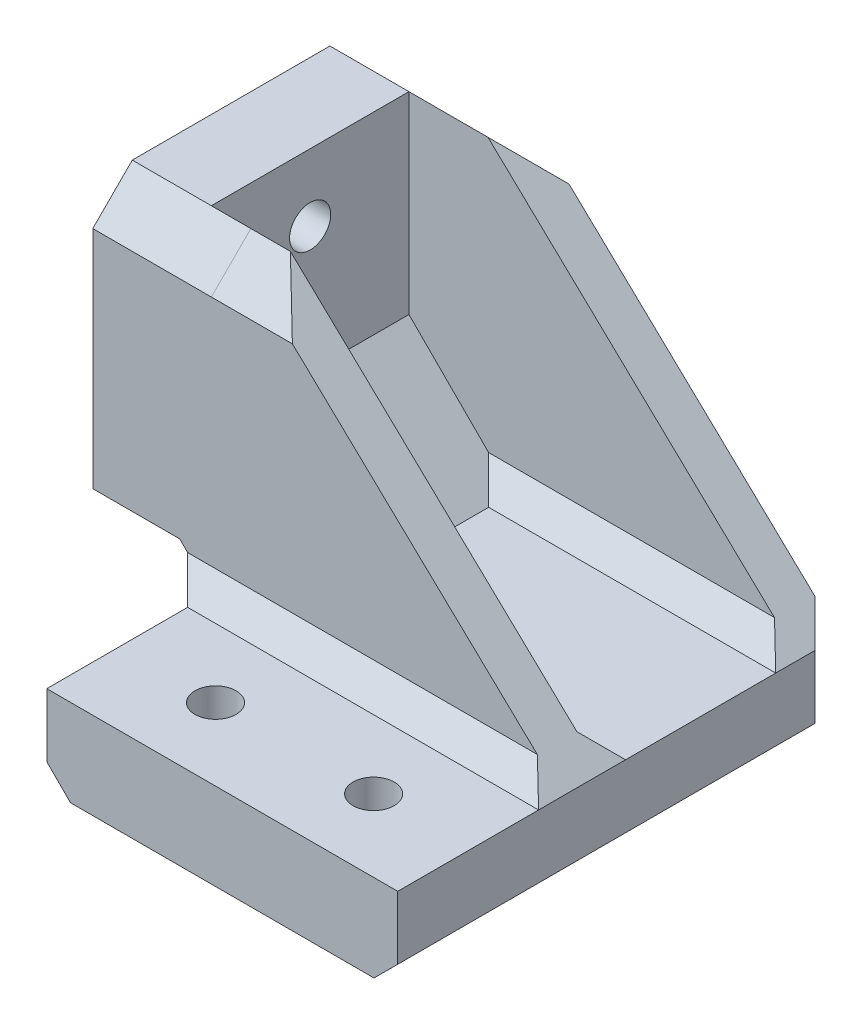
SolidWorks part; units mm, degrees
ref_plane "Front Plane" through (0, 0, 0) normal (0, 0, 1) x (1, 0, 0)
ref_plane "Top Plane" through (0, 0, 0) normal (0, 1, 0) x (1, 0, 0)
ref_plane "Right Plane" through (0, 0, 0) normal (1, 0, 0) x (0, 0, -1)
sketch "Sketch1" plane through (0, 0, 0) normal (0, 0, 1) x (1, 0, 0)
  line L0 (-22.2, 3) -> (-19.2, 0)
  line L1 (-19.2, 0) -> (19.2, 0)
  line L2 (19.2, 0) -> (22.2, 3)
  line L3 (22.2, 3) -> (22.2, 11)
  line L4 (22.2, 11) -> (-22.2, 11)
  line L5 (-22.2, 11) -> (-22.2, 3)
  line L6 (24.42, 0) -> (-24.42, 0) construction
  point P8 (0, 0)
sketch "Sketch2" plane through (0, 0, 0) normal (0, 1, 0) x (1, 0, 0)
  line L1 (-22.2, 0) -> (22.2, 0)
  line L2 (-22.2, 0) -> (-22.2, 55.82)
  line L3 (-22.2, 55.82) -> (22.2, 55.82)
  line L4 (22.2, 0) -> (22.2, 55.82)
  point P4 (0, 0)
  point P6 (0, 0)
  point P8 (0, 0)
  point P10 (-158.0606, 53.0935)
  dimension "D1" = 55.82
extrude "Boss-Extrude1" add sketch "Sketch2" along normal up to vertex (11 mm away) up to point (22.2, 11, 0)
chamfer "Chamfer1" distance 3 angle 45 2 edges at (22.2, 0, -27.91) (-22.2, 0, -27.91)
sketch "Sketch3" plane through (0, 11, 0) normal (0, 1, 0) x (1, 0, 0)
  line L0 (0, 0) -> (0, 9.15) construction
  line L1 (0, 9.15) -> (10, 9.15) construction
  line L2 (0, 9.15) -> (-10, 9.15) construction
  circle A0 centre (10, 9.15) radius 2.6
  circle A1 centre (-10, 9.15) radius 2.6
  dimension "D4" = 5.2
  dimension "D5" = 5.2
  dimension "D1" = 9.15
  dimension "D2" = 10
  dimension "D3" = 10
extrude "Cut-Extrude1" cut sketch "Sketch3" against normal through all
sketch "Sketch4" plane through (-22.2, 0, 0) normal (-1, 0, 0) x (0, 0, 1)
  line L0 (-38.32, 48.5) -> (-38.32, 11) construction
  line L1 (-55.82, 11) -> (-20.82, 11)
  line L2 (-55.82, 11) -> (-55.82, 48.5)
  line L3 (-55.82, 48.5) -> (-20.82, 48.5)
  line L4 (-20.82, 11) -> (-20.82, 48.5)
  line L5 (-55.82, 40) -> (-20.82, 40) construction
  circle A0 centre (-38.32, 40) radius 2.6
  point P11 (0, 0)
  dimension "D3" = 5.2
  dimension "D1" = 37.5
  dimension "D2" = 35
  dimension "D4" = 29
extrude "Boss-Extrude2" add sketch "Sketch4" against normal blind 5 contours L2 L1 L4 L3 | A0
sketch "Sketch8" plane through (0, 0, -55.82) normal (0, 0, -1) x (-1, 0, 0)
  line L0 (-22.2, 11) -> (22.2, 11)
  line L1 (22.2, 11) -> (22.2, 48.5)
  line L2 (22.2, 48.5) -> (17.2, 48.5)
  line L3 (17.2, 48.5) -> (-22.2, 11)
extrude "Boss-Extrude7" add sketch "Sketch8" against normal blind 5
sketch "Sketch9" plane through (0, 0, -20.82) normal (0, 0, 1) x (1, 0, 0)
  line L0 (-22.2, 11) -> (-22.2, 48.5)
  line L1 (-22.2, 48.5) -> (-17.2, 48.5)
  line L2 (-17.2, 48.5) -> (22.2, 11)
  line L3 (22.2, 11) -> (-22.2, 11)
extrude "Boss-Extrude9" add sketch "Sketch9" against normal blind 5
chamfer "Chamfer8" distance 5 angle 45 2 edges at (-19.7, 48.5, -20.82) (-19.7, 48.5, -55.82)
sketch "Sketch11" plane through (-22.2, 0, 0) normal (-1, 0, 0) x (0, 0, 1)
  line L0 (-38.32, 40) -> (-38.32, 48.5) construction
  line L1 (-50.82, 48.5) -> (-25.82, 48.5) construction
sketch "Sketch12" plane through (-22.2, 0, 0) normal (-1, 0, 0) x (0, 0, 1)
  line L1 (-55.82, 48.5) -> (-20.82, 48.5)
  line L2 (-55.82, 48.5) -> (-55.82, 15)
  line L3 (-55.82, 15) -> (-20.82, 15)
  line L4 (-20.82, 48.5) -> (-20.82, 15)
  line L5 (-17.82, 11) -> (0, 11) construction
  line L6 (-50.82, 48.5) -> (-25.82, 48.5) construction
  line M8 (-20.82, 43.5) -> (-25.82, 48.5)
  line M9 (-25.82, 48.5) -> (-50.82, 48.5)
  line M10 (-50.82, 48.5) -> (-55.82, 43.5)
  circle M14 centre (-38.32, 40) radius 2.6
  dimension "D1" = 4
extrude "Boss-Extrude11" add sketch "Sketch12" along normal blind 15 contours L3 M8 M9 M10 M14 | L2 L3 L1 M10 | L4 L1 L3 M8 region at (-22.2, 46.8333, -54.1533) region at (-22.2, 31.2596, -38.32) region at (-22.2, 46.8333, -22.4867)
chamfer "Chamfer10" distance 5 angle 45 2 edges at (-29.7, 48.5, -20.82) (-29.7, 48.5, -55.82)
sketch "Sketch13" plane through (-17.2, 0, 0) normal (1, 0, 0) x (0, 0, -1)
  line L1 (25.82, 14) -> (50.82, 14)
  line L2 (25.82, 14) -> (25.82, 48.5)
  line L3 (25.82, 48.5) -> (50.82, 48.5)
  line L4 (50.82, 14) -> (50.82, 48.5)
extrude "Cut-Extrude2" cut sketch "Sketch13" against normal blind 10
sketch "Sketch14" plane through (0, 0, -20.82) normal (0, 0, 1) x (1, 0, 0)
  line L0 (-22.2, 15) -> (-26.2, 15)
  line L1 (-37.2, 15) -> (-22.2, 15) construction
  line L2 (-26.2, 15) -> (-22.2, 11)
  line L4 (-22.2, 11) -> (-22.2, 15)
  dimension "D1" = 4
  dimension "D2" = 4
extrude "Boss-Extrude12" add sketch "Sketch14" against normal up to surface (35 mm away) up to face at (-10.8547, 17.75, -55.82)
sketch "Sketch15" plane through (0, 0, -25.82) normal (0, 0, -1) x (-1, 0, 0)
  line L0 (14.1185, 11) -> (27.2, 24.0815)
  line L2 (27.2, 48.5) -> (27.2, 15) construction
  line L3 (27.2, 24.0815) -> (27.2, 15)
  line L4 (27.2, 15) -> (22.2, 15)
  line L5 (22.2, 15) -> (22.2, 11)
  line L6 (22.2, 11) -> (14.1185, 11)
  dimension "D1" = 18.5
  dimension "D2" = 45
extrude "Boss-Extrude13" add sketch "Sketch15" along normal up to surface (25 mm away) up to face at (-17.66, 24.05, -50.82)
chamfer "Chamfer11" distance 3 angle 45 6 edges at (4.0407, 11, -50.82) (4.0407, 11, -25.82) (0, 11, -20.82) (-22.2, 7, -55.82) (22.2, 7, -55.82) (0, 0, -55.82)
